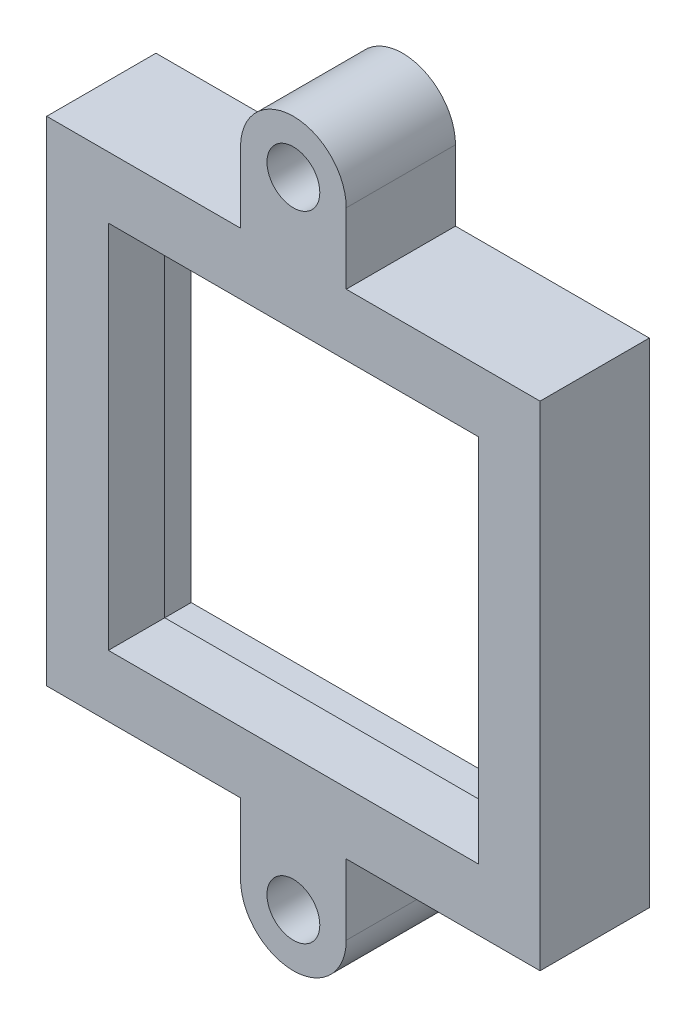
SolidWorks part; units mm, degrees
ref_plane "前视基准面" through (0, 0, 0) normal (0, 0, 1) x (1, 0, 0)
ref_plane "上视基准面" through (0, 0, 0) normal (0, 1, 0) x (1, 0, 0)
ref_plane "右视基准面" through (0, 0, 0) normal (1, 0, 0) x (0, 0, -1)
sketch "草图1" plane through (0, 0, 0) normal (0, 0, 1) x (1, 0, 0)
  line L0 (-7, 7) -> (7, 7)
  line L1 (-6, -6) -> (6, -6)
  line L2 (-6, -6) -> (-6, 6)
  line L3 (-6, 6) -> (6, 6)
  line L4 (6, -6) -> (6, 6)
  line L5 (-6, -6) -> (6, 6) construction
  line L6 (-6, 6) -> (6, -6) construction
  line L7 (7, -7) -> (7, 7)
  line L8 (-7, -7) -> (7, -7)
  line L9 (-7, -7) -> (-7, 7)
  point P0 (0, 0)
  dimension "D1" = 12
  dimension "D3" = 12
  dimension "D2" = 1
extrude "凸台-拉伸1" add sketch "草图1" along normal blind 1.5
sketch "草图2" plane through (0, -7, 0) normal (0, -1, 0) x (1, 0, 0)
  line L1 (-1.5, 0) -> (1.5, 0)
  line L2 (-1.5, 0) -> (-1.5, 1.5)
  line L3 (-1.5, 1.5) -> (1.5, 1.5)
  line L4 (1.5, 0) -> (1.5, 1.5)
  line L5 (-1.5, 0) -> (1.5, 1.5) construction
  line L6 (-1.5, 1.5) -> (1.5, 0) construction
  line L12 (-7, 1.5) -> (7, 1.5) construction
  line L13 (-7, 0) -> (7, 0) construction
  point P0 (0, 0.75)
  point P5 (0, 0)
  point P7 (0, 0)
  point P8 (0, 0)
  point P9 (0, 0)
  point P11 (0, 0.2878)
  point P15 (0, 0)
  dimension "D1" = 3
extrude "凸台-拉伸2" add sketch "草图2" along normal blind 3.5
sketch "草图3" plane through (0, 0, 1.5) normal (0, 0, 1) x (1, 0, 0)
  line L0 (1.5, -10.5) -> (-1.5, -10.5) construction
  line L1 (-1.5, -10.5) -> (-1.5, -7) construction
  line L2 (1.5, -10.5) -> (1.5, -7) construction
  line L3 (-1.5, -9) -> (-1.5, -10.5)
  line L4 (-1.5, -10.5) -> (0, -10.5)
  line L5 (0, -10.5) -> (1.5, -10.5)
  line L6 (1.5, -10.5) -> (1.5, -9)
  circle A0 centre (0, -9) radius 1.5
  circle A1 centre (0, -9) radius 0.75
  line M5 (-1.5, -7) -> (-1.5, -10.5)
  line M6 (-1.5, -10.5) -> (1.5, -10.5)
  line M7 (1.5, -10.5) -> (1.5, -7)
  dimension "D1" = 1.5
extrude "切除-拉伸1" cut sketch "草图3" against normal blind 3.5 contours A1 region at (0, -9, 1.5)
extrude "切除-拉伸2" cut sketch "草图3<3>" against normal blind 3.5 contours A0 M5 M6 | A0 M6 M7 region at (-1.1649, -10.1649, 1.5) region at (1.1649, -10.1649, 1.5)
sketch "草图3<3>" plane through (0, 0, 1.5) normal (0, 0, 1) x (1, 0, 0) same geometry as "草图3"
mirror "镜向1" about plane through (0, 0, 0) normal (0, 1, 0) of "切除-拉伸1", "切除-拉伸2", "凸台-拉伸2"
sketch "草图6" plane through (0, 0, 1.5) normal (0, 0, 1) x (1, 0, 0)
  line L0 (-1.5, -9) -> (-1.5, -7) construction
  line L1 (1.5, -9) -> (1.5, -7) construction
  line L2 (1.5, -7) -> (7, -7) construction
  line L3 (7, -7) -> (7, 7) construction
  line L4 (7, 7) -> (1.5, 7) construction
  line L5 (1.5, 9) -> (1.5, 7) construction
  line L6 (-1.5, 9) -> (-1.5, 7) construction
  line L7 (-1.5, 7) -> (-7, 7) construction
  line L8 (-7, 7) -> (-7, -7) construction
  line L9 (-7, -7) -> (-1.5, -7) construction
  line L10 (-1.5, -9) -> (-1.5, -7)
  line L11 (1.5, -9) -> (1.5, -7)
  line L12 (1.5, -7) -> (7, -7)
  line L13 (7, -7) -> (7, 7)
  line L14 (7, 7) -> (1.5, 7)
  line L15 (1.5, 9) -> (1.5, 7)
  line L16 (-1.5, 9) -> (-1.5, 7)
  line L17 (-1.5, 7) -> (-7, 7)
  line L18 (-7, 7) -> (-7, -7)
  line L19 (-7, -7) -> (-1.5, -7)
  line L21 (5.25, -5.25) -> (-5.25, -5.25)
  line L22 (5.25, -5.25) -> (5.25, 5.25)
  line L23 (5.25, 5.25) -> (-5.25, 5.25)
  line L24 (-5.25, -5.25) -> (-5.25, 5.25)
  line L25 (5.25, -5.25) -> (-5.25, 5.25) construction
  line L26 (5.25, 5.25) -> (-5.25, -5.25) construction
  arc A0 (-1.5, -9) -> (1.5, -9) centre (0, -9) ccw construction
  arc A1 (1.5, 9) -> (-1.5, 9) centre (0, 9) ccw construction
  arc A2 (-1.5, -9) -> (1.5, -9) centre (0, -9) ccw
  arc A3 (1.5, 9) -> (-1.5, 9) centre (0, 9) ccw
  circle A4 centre (0, 9) radius 0.75 construction
  circle A5 centre (0, -9) radius 0.75 construction
  circle A6 centre (0, 9) radius 0.75
  circle A7 centre (0, -9) radius 0.75
  point P10 (0, 0)
  dimension "D1" = 10.5
  dimension "D2" = 10.5
extrude "凸台-拉伸3" add sketch "草图6" along normal blind 1.6
